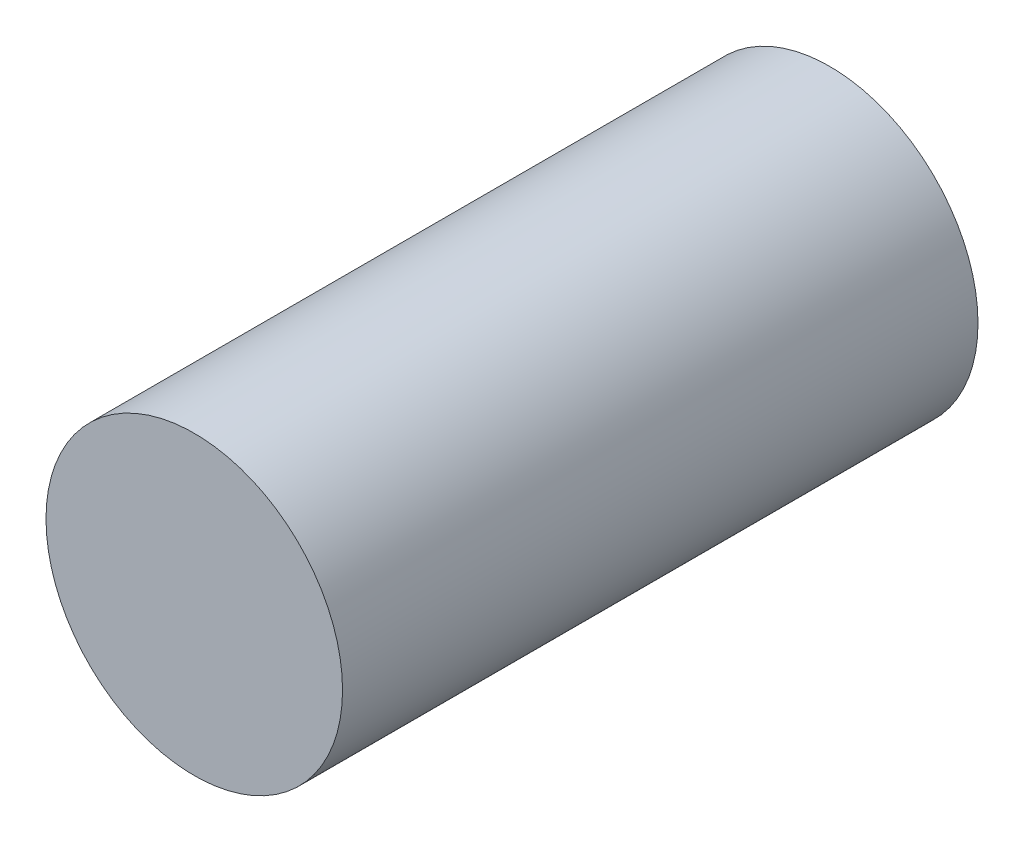
SolidWorks part; units mm, degrees
ref_plane "Płaszczyzna przednia" through (0, 0, 0) normal (0, 0, 1) x (1, 0, 0)
ref_plane "Płaszczyzna górna" through (0, 0, 0) normal (0, 1, 0) x (1, 0, 0)
ref_plane "Płaszczyzna prawa" through (0, 0, 0) normal (1, 0, 0) x (0, 0, -1)
sketch "Szkic1" plane through (0, 0, 0) normal (0, 0, 1) x (1, 0, 0)
  circle A0 centre (0, 0) radius 1.05
  dimension "D1" = 2.1
extrude "Dodanie-wyciągnięcie1" add sketch "Szkic1" along normal blind 4.5
